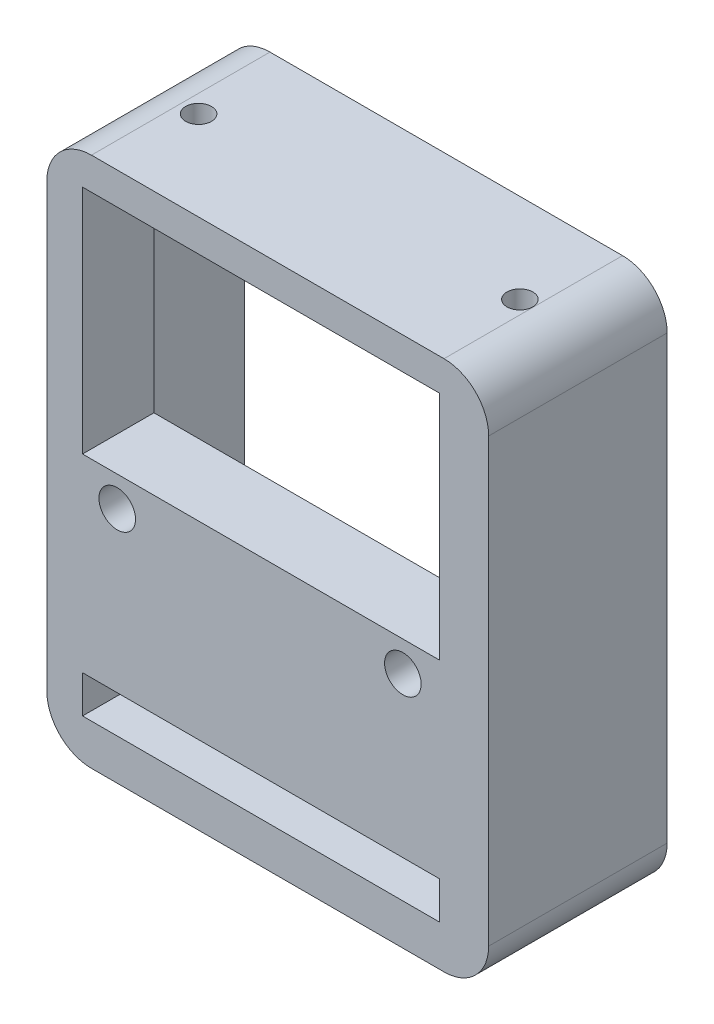
SolidWorks part; units mm, degrees
ref_plane "前视基准面" through (0, 0, 0) normal (0, 0, 1) x (1, 0, 0)
ref_plane "上视基准面" through (0, 0, 0) normal (0, 1, 0) x (1, 0, 0)
ref_plane "右视基准面" through (0, 0, 0) normal (1, 0, 0) x (0, 0, -1)
sketch "草图1" plane through (0, 0, 0) normal (0, 0, 1) x (1, 0, 0)
  line L1 (-19.75, 29.75) -> (19.75, 29.75)
  line L2 (-24.75, 24.75) -> (-24.75, -24.75)
  line L3 (-19.75, -29.75) -> (19.75, -29.75)
  line L4 (24.75, 24.75) -> (24.75, -24.75)
  line L5 (0, -29.75) -> (0, 29.75) construction
  line L6 (-24.75, 0) -> (24.75, 0) construction
  arc A0 (19.75, -29.75) -> (24.75, -24.75) centre (19.75, -24.75) ccw
  arc A1 (-24.75, -24.75) -> (-19.75, -29.75) centre (-19.75, -24.75) ccw
  arc A2 (19.75, 29.75) -> (24.75, 24.75) centre (19.75, 24.75) cw
  arc A3 (-19.75, 29.75) -> (-24.75, 24.75) centre (-19.75, 24.75) ccw
  point P0 (0, 0)
  point P8 (-24.75, -29.75)
  point P11 (24.75, 29.75)
  point P15 (-24.75, 29.75)
  dimension "D3" = 5
  dimension "D1" = 49.5
  dimension "D2" = 59.5
extrude "凸台-拉伸1" add sketch "草图1" along normal blind 20
sketch "草图2" plane through (0, 0, 0) normal (0, 0, -1) x (-1, 0, 0)
  line L1 (-22.6, 27.6) -> (22.6, 27.6)
  line L2 (-22.6, 27.6) -> (-22.6, -27.6)
  line L3 (-22.6, -27.6) -> (22.6, -27.6)
  line L4 (22.6, 27.6) -> (22.6, -27.6)
  line L5 (0, -27.6) -> (0, 27.6) construction
  line L6 (-22.6, 0) -> (22.6, 0) construction
  point P0 (0, 0)
  dimension "D1" = 45.2
  dimension "D2" = 55.2
extrude "切除-拉伸1" cut sketch "草图2" against normal blind 12
sketch "草图4" plane through (0, 0, 20) normal (0, 0, 1) x (1, 0, 0)
  line L0 (-19.75, -29.75) -> (19.75, -29.75) construction
  line L5 (-20.75, 26.15) -> (19.25, 26.15)
  line L6 (-20.75, 26.15) -> (-20.75, 0.25)
  line L7 (-20.75, 0.25) -> (19.25, 0.25)
  line L8 (19.25, 26.15) -> (19.25, 0.25)
  line L9 (-20.75, -20.965) -> (19.25, -20.965)
  line L10 (-20.75, -20.965) -> (-20.75, -25.165)
  line L11 (-20.75, -25.165) -> (19.25, -25.165)
  line L12 (19.25, -20.965) -> (19.25, -25.165)
  line L20 (19.75, 29.75) -> (-19.75, 29.75) construction
  line L21 (-24.75, 24.75) -> (-24.75, -24.75) construction
  dimension "D1" = 3.6
  dimension "D2" = 4
  dimension "D3" = 4.585
  dimension "D4" = 4.2
  dimension "D5" = 40
  dimension "D6" = 21.215
extrude "切除-拉伸2" cut sketch "草图4" against normal through all contours L8 L5 L6 L7 | L12 L9 L10 L11 region at (-0.75, 13.2, 20) region at (-0.75, -23.065, 20)
sketch "草图6" plane through (0, 0, 12) normal (0, 0, -1) x (-1, 0, 0)
  line L0 (-19.75, 29.75) -> (19.75, 29.75) construction
  line L2 (-24.75, -24.75) -> (-24.75, 24.75) construction
  circle A0 centre (16.862, -3.116) radius 1.45
  circle A1 centre (-15.138, -3.116) radius 1.45
  dimension "D4" = 2.9
  dimension "D1" = 32
  dimension "D2" = 32.866
  dimension "D3" = 9.612
extrude "切除-拉伸4" cut sketch "草图6" against normal through all
sketch "草图7" plane through (0, 0, 20) normal (0, 0, 1) x (1, 0, 0)
  circle A0 centre (-16.862, -3.116) radius 2.05
  circle A1 centre (15.138, -3.116) radius 2.05
  dimension "D1" = 4.1
extrude "切除-拉伸5" cut sketch "草图7" against normal blind 6
sketch "草图10" plane through (0, 0, 12) normal (0, 0, -1) x (-1, 0, 0)
  line L0 (-22.6, -27.6) -> (22.6, -27.6) construction
  line L5 (22.6, -27.6) -> (22.6, 27.6) construction
  line L6 (22.6, 27.6) -> (-22.6, 27.6) construction
  line L7 (-22.6, 27.6) -> (-22.6, -27.6) construction
  line L8 (-22.6, -27.6) -> (22.6, -27.6)
  line L9 (22.6, -27.6) -> (22.6, 27.6)
  line L10 (22.6, 27.6) -> (-22.6, 27.6)
  line L11 (-22.6, 27.6) -> (-22.6, -27.6)
  line L12 (-21.6, 26.6) -> (-21.6, -26.6)
  line L13 (-21.6, -26.6) -> (21.6, -26.6)
  line L14 (21.6, -26.6) -> (21.6, 26.6)
  line L15 (21.6, 26.6) -> (-21.6, 26.6)
  dimension "D1" = 1
extrude "凸台-拉伸2" [suppressed] add sketch "草图10" along normal blind 3.5
sketch "草图8" plane through (0, 29.75, 0) normal (0, 1, 0) x (1, 0, 0)
  line L0 (-24.75, -20) -> (-24.75, 0) construction
  line L1 (19.75, 0) -> (-19.75, 0) construction
  circle A0 centre (-17.75, -10) radius 1.45
  circle A1 centre (18.25, -10) radius 1.45
  dimension "D4" = 2.9
  dimension "D1" = 36
  dimension "D2" = 7
  dimension "D3" = 10
extrude "切除-拉伸6" cut sketch "草图8" against normal blind 6
sketch "草图9" plane through (0, -29.75, 0) normal (0, -1, 0) x (1, 0, 0)
  line L0 (0, 20) -> (0, 0) construction
  line L1 (-19.75, 20) -> (19.75, 20) construction
  circle A0 centre (-10, 10) radius 1.45
  circle A1 centre (10, 10) radius 1.45
  dimension "D3" = 2.9
  dimension "D1" = 10
  dimension "D2" = 10
extrude "切除-拉伸7" cut sketch "草图9" against normal blind 6
